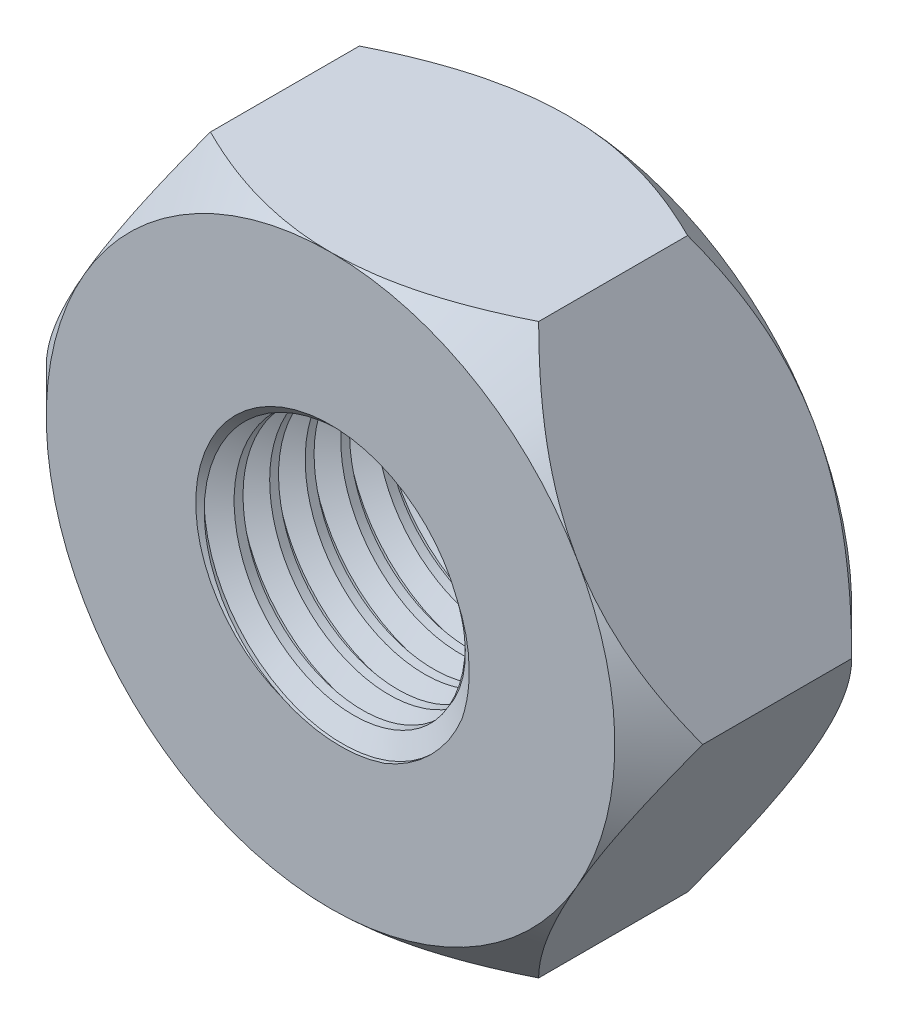
SolidWorks part; units mm, degrees
ref_plane "Front Plane" through (0, 0, 0) normal (0, 0, 1) x (1, 0, 0)
ref_plane "Top Plane" through (0, 0, 0) normal (0, 1, 0) x (1, 0, 0)
ref_plane "Right Plane" through (0, 0, 0) normal (1, 0, 0) x (0, 0, -1)
sketch "Sketch1" plane through (0, 0, 0) normal (0, 0, 1) x (1, 0, 0)
  line L1 (13.8564, 0) -> (6.9282, 12)
  line L2 (6.9282, 12) -> (-6.9282, 12)
  line L3 (-6.9282, 12) -> (-13.8564, 0)
  line L4 (-13.8564, 0) -> (-6.9282, -12)
  line L5 (-6.9282, -12) -> (6.9282, -12)
  line L6 (6.9282, -12) -> (13.8564, 0)
  circle A0 centre (0, 0) radius 12 construction
  dimension "D1" = 24
extrude "Boss-Extrude1" add sketch "Sketch1" along normal mid plane 10
sketch "Sketch2" plane through (0, 0, 5) normal (0, 0, 1) x (1, 0, 0)
  line L0 (-6.9282, 12) -> (-13.8564, 0) construction
  circle A0 centre (0, 0) radius 12
extrude "Cut-Extrude1" cut sketch "Sketch2" against normal blind 10 draft 45 flip side to cut
ref_plane "Plane1" through (0, 0, 0) normal (0, 0, 1) x (1, 0, 0)
mirror "Mirror1" about plane through (0, 0, 0) normal (0, 0, 1) of "Cut-Extrude1"
sketch "Sketch3" plane through (0, 0, 5) normal (0, 0, 1) x (1, 0, 0)
  circle A0 centre (0, 0) radius 5.19
  dimension "D1" = 10.38
extrude "Cut-Extrude2" cut sketch "Sketch3" against normal through all
chamfer "Chamfer2" distance 0.5 angle 45 2 edges at (5.19, 0, -5) (5.19, 0, 5)
thread "Thread3" pitch 1.5 method cut profile "Thread Profile3" start angle 0, offset 5, length 0, pitch 1.5, diameter 10.38
ref_plane "Plane4" through (-5.19, 0, 9.5) normal (0, -1, 0) x (-1, 0, 0)
sketch "Thread Profile3" plane through (-5.19, 0, 9.5) normal (0, -1, 0) x (-1, 0, 0)
  line L0 (0, 0) -> (0, 1.5) construction
  line L1 (0, 0) -> (0.8119, 0.4687)
  line L2 (0.8119, 0.4687) -> (0.8119, 0.6562)
  line L3 (0.8119, 0.6562) -> (0, 1.125)
  line L4 (0.8119, 0.5625) -> (0, 0.5625) construction
  line L11 (0, 0) -> (0, 1.125)
  point P2 (0, 0)
  dimension "Pitch" = 1.5
  dimension "Profile_Angle" = 60
  dimension "Profile_Land" = 0.1875
  dimension "Profile_Height" = 0.8119
